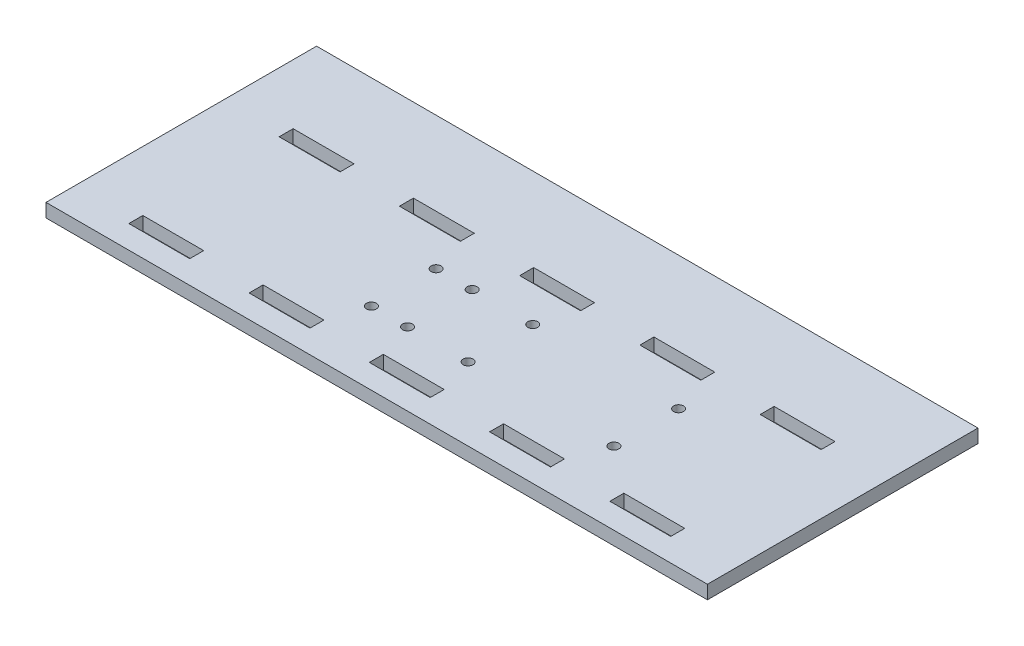
SolidWorks part; units mm, degrees
ref_plane "Front Plane" through (0, 0, 0) normal (0, 0, 1) x (1, 0, 0)
ref_plane "Top Plane" through (0, 0, 0) normal (0, 1, 0) x (1, 0, 0)
ref_plane "Right Plane" through (0, 0, 0) normal (1, 0, 0) x (0, 0, -1)
sketch "Sketch2" plane through (0, 0, 0) normal (0, 1, 0) x (1, 0, 0)
  line L3 (110, 45) -> (-110, 45)
  line L4 (110, 45) -> (110, -45)
  line L5 (110, -45) -> (-110, -45)
  line L6 (-110, 45) -> (-110, -45)
  line L7 (110, 45) -> (-110, -45) construction
  line L8 (110, -45) -> (-110, 45) construction
  point P0 (0, 0)
  dimension "D1" = 220
  dimension "D2" = 90
extrude "Boss-Extrude1" add sketch "Sketch2" along normal blind 4.5
sketch "Sketch3" plane through (0, 0, 0) normal (0, -1, 0) x (1, 0, 0)
  line L0 (0, 0) -> (0, -15) construction
  line L1 (50.125, -12.675) -> (50.125, -17.325)
  line L2 (10.125, -12.675) -> (-10.125, -12.675)
  line L3 (10.125, -12.675) -> (10.125, -17.325)
  line L4 (10.125, -17.325) -> (-10.125, -17.325)
  line L5 (-10.125, -12.675) -> (-10.125, -17.325)
  line L6 (10.125, -12.675) -> (-10.125, -17.325) construction
  line L7 (10.125, -17.325) -> (-10.125, -12.675) construction
  line L8 (50.125, -12.675) -> (29.875, -12.675)
  line L9 (29.875, -12.675) -> (29.875, -17.325)
  line L10 (50.125, -17.325) -> (29.875, -17.325)
  line L11 (90.125, -12.675) -> (90.125, -17.325)
  line L12 (90.125, -12.675) -> (69.875, -12.675)
  line L13 (69.875, -12.675) -> (69.875, -17.325)
  line L14 (90.125, -17.325) -> (69.875, -17.325)
  line L15 (10.125, -12.675) -> (50.125, -12.675) construction
  line L16 (-90.125, -17.325) -> (-69.875, -17.325)
  line L17 (-69.875, -12.675) -> (-69.875, -17.325)
  line L18 (-90.125, -12.675) -> (-69.875, -12.675)
  line L19 (-90.125, -12.675) -> (-90.125, -17.325)
  line L20 (-50.125, -17.325) -> (-29.875, -17.325)
  line L21 (-29.875, -12.675) -> (-29.875, -17.325)
  line L22 (-50.125, -12.675) -> (-29.875, -12.675)
  line L23 (-50.125, -12.675) -> (-50.125, -17.325)
  line L24 (0, 0) -> (0, 10) construction
  line L25 (0, 10) -> (-14.7938, 10) construction
  line L26 (10.125, 32.675) -> (50.125, 32.675) construction
  line L27 (10.125, 37.325) -> (-10.125, 32.675) construction
  line L28 (10.125, 32.675) -> (-10.125, 37.325) construction
  line L29 (-50.125, 32.675) -> (-50.125, 37.325)
  line L30 (-50.125, 32.675) -> (-29.875, 32.675)
  line L31 (-29.875, 32.675) -> (-29.875, 37.325)
  line L32 (-50.125, 37.325) -> (-29.875, 37.325)
  line L33 (-90.125, 32.675) -> (-90.125, 37.325)
  line L34 (-90.125, 32.675) -> (-69.875, 32.675)
  line L35 (-69.875, 32.675) -> (-69.875, 37.325)
  line L36 (-90.125, 37.325) -> (-69.875, 37.325)
  line L37 (90.125, 37.325) -> (69.875, 37.325)
  line L38 (69.875, 32.675) -> (69.875, 37.325)
  line L39 (90.125, 32.675) -> (69.875, 32.675)
  line L40 (90.125, 32.675) -> (90.125, 37.325)
  line L41 (50.125, 37.325) -> (29.875, 37.325)
  line L42 (29.875, 32.675) -> (29.875, 37.325)
  line L43 (50.125, 32.675) -> (29.875, 32.675)
  line L44 (-10.125, 32.675) -> (-10.125, 37.325)
  line L45 (10.125, 37.325) -> (-10.125, 37.325)
  line L46 (10.125, 32.675) -> (10.125, 37.325)
  line L47 (10.125, 32.675) -> (-10.125, 32.675)
  line L48 (50.125, 32.675) -> (50.125, 37.325)
  dimension "D1" = 15
  dimension "D2" = 20.25
  dimension "D3" = 4.65
  dimension "D5" = 40
  dimension "D6" = 10
  dimension "D4" = 3
extrude "Cut-Extrude1" cut sketch "Sketch3" against normal through all
sketch "Sketch4" plane through (0, 0, 0) normal (0, -1, 0) x (1, 0, 0)
  line L0 (0, 5) -> (40, 5) construction
  line L1 (0, 0) -> (0, 5) construction
  line L2 (60, 12.5) -> (20, 12.5)
  line L3 (60, 12.5) -> (60, -2.5)
  line L4 (60, -2.5) -> (20, -2.5)
  line L5 (20, 12.5) -> (20, -2.5)
  line L6 (60, 12.5) -> (20, -2.5) construction
  line L7 (60, -2.5) -> (20, 12.5) construction
  dimension "D1" = 40
  dimension "D2" = 15
  dimension "D3" = 5
  dimension "D4" = 40
extrude "Input link cut" [suppressed] cut sketch "Sketch4" against normal through all
sketch "Sketch5" plane through (0, 0, 0) normal (0, -1, 0) x (1, 0, 0)
  line L0 (54.65, 37.25) -> (54.65, -17.25) construction
  line L1 (56.9, 37.25) -> (52.4, 37.25) construction
  line L2 (52.4, -17.25) -> (56.9, -17.25) construction
  line L3 (6.15, 32.75) -> (6.15, -17.325) construction
  line L4 (3.9, 32.75) -> (8.4, 32.75) construction
  line L5 (-10.125, -17.325) -> (10.125, -17.325) construction
  line L6 (-26, -17.25) -> (-26, 37.25) construction
  line L7 (-27.75, -17.25) -> (-24.25, -17.25) construction
  line L8 (-24.25, 37.25) -> (-27.75, 37.25) construction
  line L9 (-14, -17.25) -> (-14, 37.25) construction
  line L10 (-15.75, -17.25) -> (-12.25, -17.25) construction
  line L11 (-12.25, 37.25) -> (-15.75, 37.25) construction
  line L12 (-26, 20.75) -> (58.5718, 20.75) construction
  line L13 (-10, 32.75) -> (-30, 32.75) construction
  line L14 (-26, 10) -> (-62.5697, 10) construction
  circle A0 centre (-26, 20.75) radius 1.65
  circle A1 centre (-14, 20.75) radius 1.65
  circle A2 centre (6.15, 20.75) radius 1.65
  circle A3 centre (54.65, 20.75) radius 1.65
  circle A4 centre (54.65, -0.75) radius 1.65
  circle A5 centre (6.15, -0.75) radius 1.65
  circle A6 centre (-14, -0.75) radius 1.65
  circle A7 centre (-26, -0.75) radius 1.65
  dimension "D2" = 3.3
  dimension "D1" = 12
extrude "Bracket holes" cut sketch "Sketch5" against normal through all
